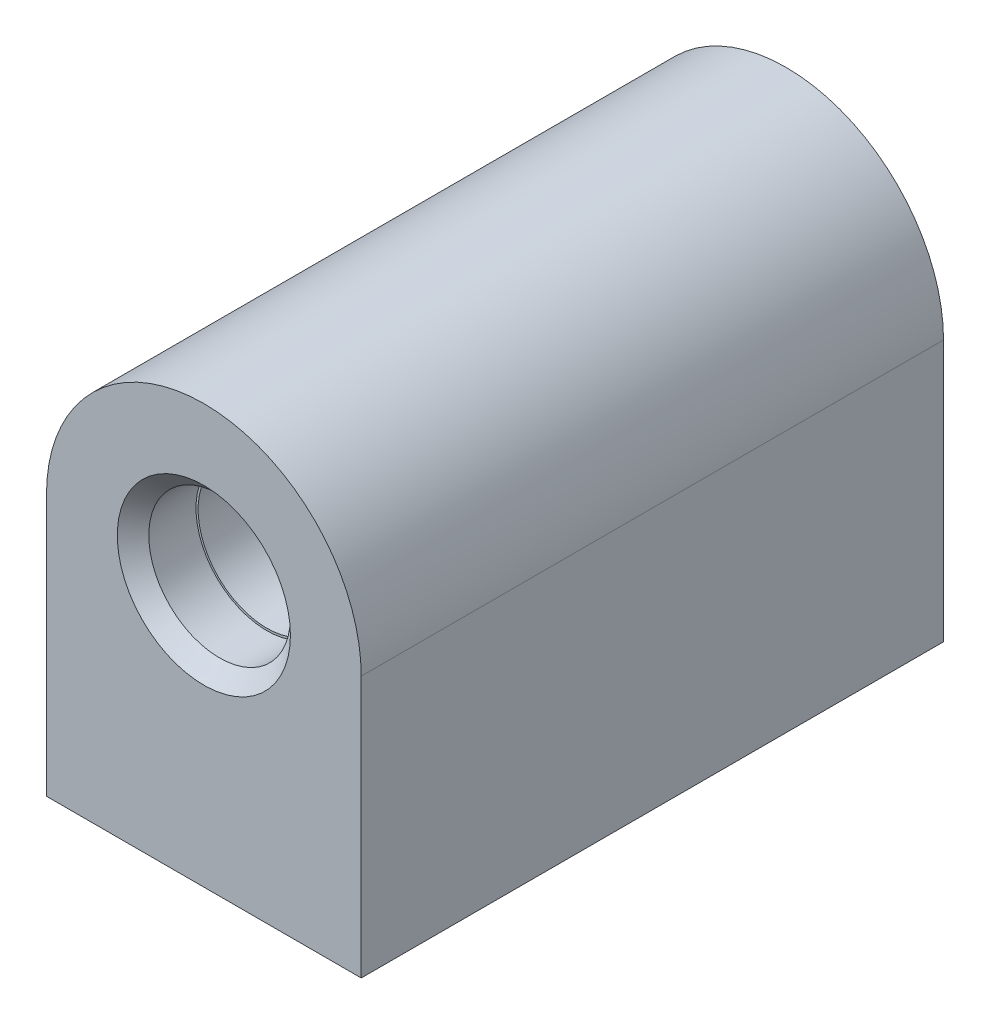
SolidWorks part; units mm, degrees
ref_plane "Alzado" through (0, 0, 0) normal (0, 0, 1) x (1, 0, 0)
ref_plane "Planta" through (0, 0, 0) normal (0, 1, 0) x (1, 0, 0)
ref_plane "Vista lateral" through (0, 0, 0) normal (1, 0, 0) x (0, 0, -1)
sketch "Croquis1" plane through (0, 0, 0) normal (0, 0, 1) x (1, 0, 0)
  circle A0 centre (0, 0) radius 4.365
  circle A1 centre (0, 0) radius 4.85
  circle A2 centre (0, 0) radius 10
  circle A3 centre (0, 0) radius 5
  circle A4 centre (0, 0) radius 8.5
  dimension "D1" = 8.73
  dimension "D2" = 9.7
  dimension "D3" = 20
  dimension "D4" = 1.5
  dimension "10" = 10
extrude "Saliente-Extruir1" add sketch "Croquis1" along normal blind 37 contours A0 | A2 region at (0, 0, 0)
extrude "Cortar-Extruir1" cut sketch "Croquis1<3>" along normal blind 5 from offset 1 contours A4
sketch "Croquis1<3>" plane through (0, 0, 0) normal (0, 0, 1) x (1, 0, 0) same geometry as "Croquis1"
extrude "Cortar-Extruir2" cut sketch "Croquis1<4>" along normal blind 5 from offset 7 contours A4
sketch "Croquis1<4>" plane through (0, 0, 0) normal (0, 0, 1) x (1, 0, 0) same geometry as "Croquis1"
extrude "Cortar-Extruir3" cut sketch "Croquis1<5>" against normal blind 5 from offset 18 contours A4
sketch "Croquis1<5>" plane through (0, 0, 0) normal (0, 0, 1) x (1, 0, 0) same geometry as "Croquis1"
extrude "Cortar-Extruir4" cut sketch "Croquis1<6>" along normal blind 5 from offset 19 contours A4
sketch "Croquis1<6>" plane through (0, 0, 0) normal (0, 0, 1) x (1, 0, 0) same geometry as "Croquis1"
extrude "Cortar-Extruir5" cut sketch "Croquis1<7>" against normal blind 5 from offset 30 contours A4
sketch "Croquis1<7>" plane through (0, 0, 0) normal (0, 0, 1) x (1, 0, 0) same geometry as "Croquis1"
chamfer "Chaflán1" distance 5 angle 45 5 edges at (8.5, 0, 13) (8.5, 0, 7) (8.5, 0, 1) (8.5, 0, 25) (8.5, 0, 19)
sketch "Croquis4" plane through (0, 0, 0) normal (0, 0, 1) x (1, 0, 0)
  circle A0 centre (0, 0) radius 4.5
  dimension "D1" = 9
extrude "Cortar-Extruir6" cut sketch "Croquis4" against normal blind 4 from surface starting at face at (10, 0, 37)
chamfer "Chaflán2" distance 1 angle 45 1 edges at (4.5, 0, 37)
sketch "Croquis5" plane through (0, 0, 0) normal (0, 0, 1) x (1, 0, 0)
  line L1 (-10, 0) -> (10, 0)
  line L2 (-10, 0) -> (-10, -16.6113)
  line L3 (-10, -16.6113) -> (10, -16.6113)
  line L4 (10, 0) -> (10, -16.6113)
  circle A0 centre (0, 0) radius 4.365
  circle A1 centre (0, 0) radius 4.85
  circle A2 centre (0, 0) radius 10
  circle A3 centre (0, 0) radius 5
  circle A4 centre (0, 0) radius 8.5
  dimension "D1" = 8.73
  dimension "D2" = 9.7
  dimension "D3" = 20
  dimension "D4" = 1.5
  dimension "10" = 10
extrude "Saliente-Extruir2" add sketch "Croquis5" along normal blind 37 contours A2 L2 L3 L4 region at (0, -11.9482, 0)
sketch "Croquis6" plane through (0, 0, 0) normal (0, 1, 0) x (1, 0, 0)
  line L0 (-10, 0) -> (10, -37) construction
  line L2 (0, -25.1973) -> (5.8, -21.8486)
  line L3 (5.8, -21.8486) -> (5.8, -15.1514)
  line L4 (5.8, -15.1514) -> (0, -11.8027)
  line L5 (0, -11.8027) -> (-5.8, -15.1514)
  line L6 (-5.8, -15.1514) -> (-5.8, -21.8486)
  line L7 (-5.8, -21.8486) -> (0, -25.1973)
  circle A0 centre (0, -18.5) radius 3.3
  circle A1 centre (0, -18.5) radius 5.8 construction
  dimension "D1" = 6.6
  dimension "D2" = 11.6
extrude "Cortar-Extruir7" cut sketch "Croquis6" against normal blind 116 from offset 10 contours A0 offset against normal yes
extrude "Cortar-Extruir8" cut sketch "Croquis6<3>" against normal blind 5 from offset 12 offset against normal yes
sketch "Croquis6<3>" plane through (0, 0, 0) normal (0, 1, 0) x (1, 0, 0) same geometry as "Croquis6"
